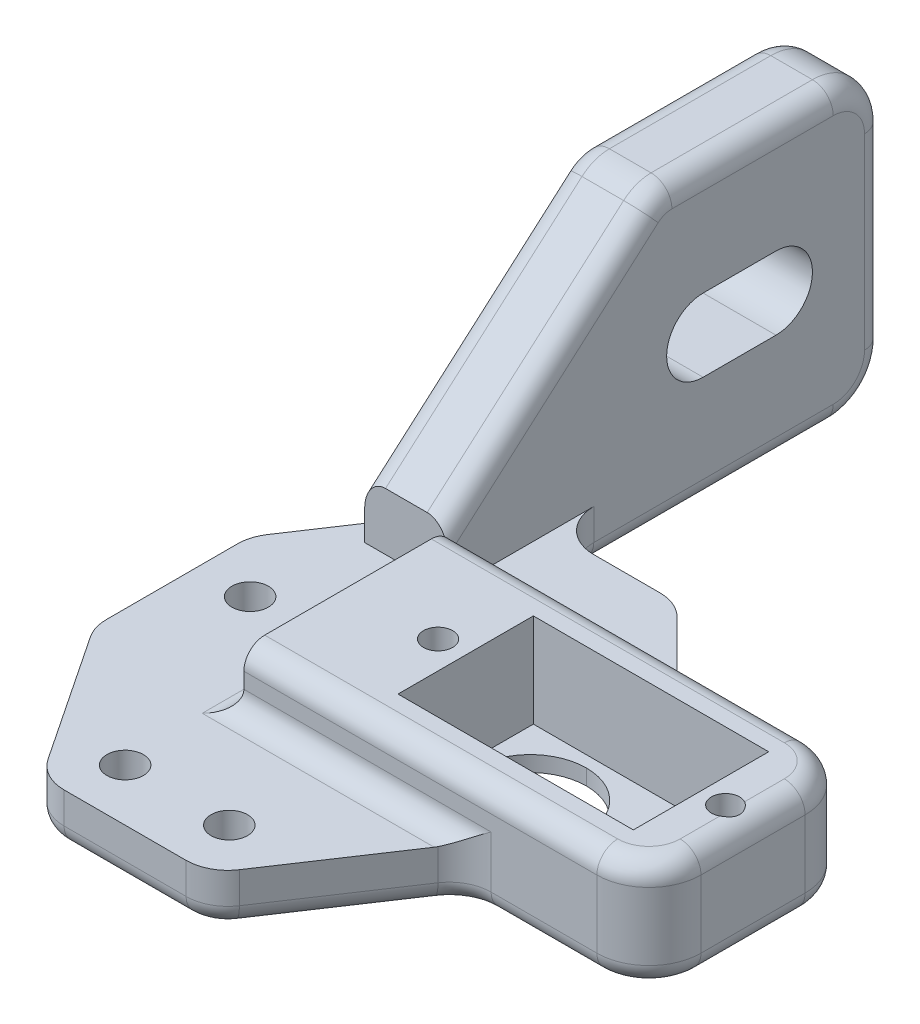
SolidWorks part; units mm, degrees
ref_plane "Front Plane" through (0, 0, 0) normal (0, 0, 1) x (1, 0, 0)
ref_plane "Top Plane" through (0, 0, 0) normal (0, 1, 0) x (1, 0, 0)
ref_plane "Right Plane" through (0, 0, 0) normal (1, 0, 0) x (0, 0, -1)
sketch "Sketch1" plane through (0, 0, 0) normal (0, 1, 0) x (1, 0, 0)
  line L0 (0, 0) -> (20.5534, 0) construction
  line L1 (20.5534, 10) -> (20.5534, -10)
  line L2 (20.5534, 10) -> (-3.4466, 10)
  line L3 (-3.4466, 10) -> (-13.4451, 19.9985)
  line L4 (-13.4451, 19.9985) -> (-29.4451, 19.9985)
  line L5 (-29.4451, 19.9985) -> (-39.4464, 4.9966)
  line L6 (-39.4464, 4.9966) -> (-39.4464, -10.0034)
  line L7 (-39.4464, -10.0034) -> (-29.4451, -25.0053)
  line L8 (-29.4451, -25.0053) -> (-13.4451, -25.0053)
  line L9 (-13.4451, -25.0053) -> (-3.4416, -10)
  line L10 (-3.4416, -10) -> (20.5534, -10)
  point P5 (20.5534, 0)
  dimension "D1" = 20
  dimension "D2" = 24
  dimension "D3" = 14.14
  dimension "D4" = 225
  dimension "D5" = 16
  dimension "D6" = 18.03
  dimension "D7" = 15
  dimension "D8" = 146.31
  dimension "D9" = 18.03
  dimension "D10" = 16
  dimension "D11" = 123.69
  dimension "D12" = 123.69
  dimension "D13" = 18.0341
extrude "Boss-Extrude1" add sketch "Sketch1" against normal blind 5
sketch "Sketch2" plane through (0, 0, 0) normal (0, 1, 0) x (1, 0, 0)
  line L0 (20.5534, 0) -> (-55.4537, 0) construction
  line L1 (20.5534, -10) -> (20.5534, 10) construction
  line L2 (-39.4464, 4.9966) -> (-39.4464, -10.0034) construction
  line L3 (-39.4464, -10.0034) -> (-3.4416, -10) construction
  line L4 (-21.444, -10.0017) -> (-21.444, -20.0053) construction
  line L5 (-26.444, -20.0053) -> (-16.444, -20.0053) construction
  line L6 (-29.4451, -25.0053) -> (-13.4451, -25.0053) construction
  line L8 (-12.9466, 5.4) -> (-2.1466, 5.4)
  line L9 (-12.9466, 5.4) -> (-12.9466, -5.4)
  line L10 (-12.9466, -5.4) -> (-2.1466, -5.4)
  line L11 (-2.1466, 5.4) -> (-2.1466, -5.4)
  line L12 (-12.9466, 5.4) -> (-2.1466, -5.4) construction
  line L13 (-12.9466, -5.4) -> (-2.1466, 5.4) construction
  circle A0 centre (-34.4464, 0) radius 1.75
  circle A1 centre (-26.444, -20.0053) radius 1.75
  circle A2 centre (-16.444, -20.0053) radius 1.75
  point P18 (-21.444, -20.0053)
  point P22 (-7.5466, 0)
  dimension "D2" = 3.5
  dimension "D5" = 3.5
  dimension "D1" = 5
  dimension "D3" = 10
  dimension "D4" = 5
  dimension "D6" = 22.7
  dimension "D7" = 10.8
  dimension "D8" = 10.8
extrude "Cut-Extrude2" cut sketch "Sketch2" along normal through all and the other way through all
fillet "Fillet1" 2 edges at (-12.9466, -2.5, -5.4) (-12.9466, -2.5, 5.4) type full round first side face at (-7.5466, -2.5, -5.4) second side face at (-7.5466, -2.5, 5.4) middle face at (-12.9466, -2.5, 0)
fillet "Fillet2" 2 edges at (-2.1466, -2.5, -5.4) (-2.1466, -2.5, 5.4) type full round first side face at (-4.8466, -2.5, -5.4) second side face at (-4.8466, -2.5, 5.4) middle face at (-2.1466, -2.5, 0)
fillet "Fillet3" 2 edges at (20.5534, -2.5, -10) (20.5534, -2.5, 10) type full round first side face at (8.5534, -2.5, -10) second side face at (8.5559, -2.5, 10) middle face at (20.5534, -2.5, 0)
sketch "Sketch3" plane through (0, 0, 0) normal (0, 1, 0) x (1, 0, 0)
  line L0 (-12.9466, 0) -> (-2.1466, 0) construction
  line L1 (10.5534, 10) -> (-3.4466, 10) construction
  line L2 (-19.0466, -6.5) -> (3.9534, -6.5)
  line L3 (-19.0466, -6.5) -> (-19.0466, 6.5)
  line L4 (-19.0466, 6.5) -> (3.9534, 6.5)
  line L5 (3.9534, -6.5) -> (3.9534, 6.5)
  line L6 (-19.0466, -6.5) -> (3.9534, 6.5) construction
  line L7 (-19.0466, 6.5) -> (3.9534, -6.5) construction
  line L8 (-25.0466, -10) -> (9.9534, -10)
  line L9 (-25.0466, -10) -> (-25.0466, 10)
  line L10 (-25.0466, 10) -> (9.9534, 10)
  line L11 (9.9534, -10) -> (9.9534, 10)
  line L12 (-25.0466, -10) -> (9.9534, 10) construction
  line L13 (-25.0466, 10) -> (9.9534, -10) construction
  arc A0 (-7.5466, 5.4) -> (-7.5466, -5.4) centre (-7.5466, 0) ccw construction
  arc A1 (-7.5466, -5.4) -> (-7.5466, 5.4) centre (-7.5466, 0) ccw construction
  point P8 (-7.5466, 0)
  point P13 (-7.5466, 0)
  dimension "D1" = 6
  dimension "D2" = 13
  dimension "D3" = 23
extrude "Boss-Extrude4" add sketch "Sketch3" along normal blind 5.5
sketch "Sketch4" plane through (0, 0, 0) normal (0, 1, 0) x (1, 0, 0)
  line L4 (-19.0466, 6.5) -> (-19.0466, -6.5)
  line L5 (-19.0466, -6.5) -> (3.9534, -6.5)
  line L6 (3.9534, -6.5) -> (3.9534, 6.5)
  line L7 (3.9534, 6.5) -> (-19.0466, 6.5)
  line L8 (-19.0466, 6.5) -> (-19.0466, -6.5)
  line L9 (-19.0466, -6.5) -> (3.9534, -6.5)
  line L10 (3.9534, -6.5) -> (3.9534, 6.5)
  line L11 (3.9534, 6.5) -> (-19.0466, 6.5)
  dimension "D1" = 0
extrude "Cut-Extrude3" cut sketch "Sketch4" against normal blind 3.5
sketch "Sketch5" plane through (0, 0, 0) normal (0, 1, 0) x (1, 0, 0)
  line L3 (9.9534, 10) -> (9.9534, -10)
  line L4 (9.9534, -10) -> (10.5534, -10)
  line L5 (10.5534, 10) -> (9.9534, 10)
  line L6 (9.9534, 10) -> (9.9534, -10)
  line L7 (9.9534, -10) -> (10.5534, -10)
  line L8 (10.5534, 10) -> (9.9534, 10)
  arc A1 (10.5534, -10) -> (10.5534, 10) centre (10.5534, 0) ccw
  arc A2 (10.5534, -10) -> (10.5534, 10) centre (10.5534, 0) ccw
  dimension "D1" = 0
extrude "Cut-Extrude4" cut sketch "Sketch5" against normal through all body kept at (9.9534, 5.5, 10)
fillet "Fillet4" radius 4 2 edges at (9.9534, 0.25, 10) (9.9534, 0.25, -10)
sketch "Sketch6" plane through (0, 0, -19.9985) normal (0, 0, -1) x (-1, 0, 0)
  line L0 (13.4451, -5) -> (29.4451, -5) construction
  line L1 (25.4451, -5) -> (33.4451, -5)
  line L2 (25.4451, -5) -> (25.4451, 23)
  line L3 (25.4451, 23) -> (33.4451, 23)
  line L4 (33.4451, -5) -> (33.4451, 23)
  line L5 (29.4451, -5) -> (29.4451, 0) construction
  point P8 (29.4451, -2.5)
  dimension "D1" = 4
  dimension "D2" = 4
  dimension "D3" = 28
extrude "Boss-Extrude5" add sketch "Sketch6" along normal blind 32
sketch "Sketch7" plane through (-25.4451, 0, 0) normal (1, 0, 0) x (0, 0, -1)
  line L0 (51.9985, -5) -> (19.9985, -5) construction
  line L1 (51.9985, 23) -> (51.9985, -5) construction
  line L2 (33.4985, 9) -> (42.4985, 9) construction
  circle A0 centre (37.9985, 9) radius 2.5
  circle A1 centre (33.4985, 9) radius 1.3
  circle A2 centre (42.4985, 9) radius 1.3
  point P9 (37.9985, 9)
  dimension "D1" = 5
  dimension "D5" = 2.6
  dimension "D2" = 14
  dimension "D3" = 14
  dimension "D4" = 9
extrude "Cut-Extrude5" cut sketch "Sketch7" against normal through all
fillet "Fillet5" radius 5 2 edges at (-29.4451, -5, -51.9985) (-29.4451, 23, -51.9985)
sketch "Sketch8" plane through (-25.4451, 0, 0) normal (1, 0, 0) x (0, 0, -1)
  line L0 (10, 5.5) -> (19.9985, 23)
  line L1 (19.9985, 23) -> (19.9985, -5)
  line L2 (19.9985, -5) -> (10, -5)
  line L3 (10, -5) -> (10, 5.5)
extrude "Boss-Extrude6" add sketch "Sketch8" against normal up to surface (8 mm away) up to face at (-33.4451, 9, -43.7985)
sketch "Sketch9" plane through (-25.4451, 0, 0) normal (1, 0, 0) x (0, 0, -1)
  line L0 (40.4985, 9) -> (35.4985, 9) construction
  line L2 (44.9985, 12.5) -> (30.9985, 12.5)
  line L3 (44.9985, 12.5) -> (44.9985, 5.5)
  line L4 (44.9985, 5.5) -> (30.9985, 5.5)
  line L5 (30.9985, 12.5) -> (30.9985, 5.5)
  line L6 (44.9985, 12.5) -> (30.9985, 5.5) construction
  line L7 (44.9985, 5.5) -> (30.9985, 12.5) construction
  circle A0 centre (37.9985, 9) radius 2.5 construction
  point P5 (37.9985, 9)
  dimension "D1" = 7
  dimension "D2" = 14
extrude "Cut-Extrude6" cut sketch "Sketch9" against normal blind 7
fillet "Fillet7" 2 edges at (-28.9451, 5.5, -44.9985) (-28.9451, 12.5, -44.9985) type full round first side face at (-28.9451, 5.5, -37.9985) second side face at (-28.9451, 12.5, -37.9985) middle face at (-28.9451, 9, -44.9985)
fillet "Fillet8" 2 edges at (-28.9451, 12.5, -30.9985) (-28.9451, 5.5, -30.9985) type full round first side face at (-28.9451, 12.5, -36.2485) second side face at (-28.9451, 5.5, -36.2485) middle face at (-28.9451, 9, -30.9985)
sketch "Sketch10" plane through (-25.4451, 0, 0) normal (1, 0, 0) x (0, 0, -1)
  line L0 (10, 5.5) -> (29.9985, 23)
  line L1 (46.9985, 23) -> (19.9985, 23) construction
  line L2 (29.9985, 23) -> (19.9985, 23)
  line L3 (19.9985, 23) -> (10, 5.5)
  dimension "D1" = 10
extrude "Cut-Extrude7" cut sketch "Sketch10" against normal through all
fillet "Fillet9" radius 4 6 edges at (-13.4451, -2.5, 25.0053) (-29.4451, -2.5, 25.0053) (-39.4464, -2.5, 10.0034) (-39.4464, -2.5, -4.9966) (-33.4451, -2.5, -13.9985) (-29.4451, 23, -29.9985)
fillet "Fillet10" radius 4 1 edges at (-3.4416, -2.5, 10)
fillet "Fillet11" radius 4 3 edges at (-25.4451, -2.5, -19.9985) (-13.4451, -2.5, -19.9985) (-3.4466, -2.5, -10)
sketch "Sketch11" plane through (0, -3.5, 0) normal (0, 1, 0) x (1, 0, 0)
  line L0 (-19.0466, -6.5) -> (3.9534, -6.5) construction
  line L1 (-19.0466, 6.5) -> (-13.7466, 6.5)
  line L2 (-19.0466, 6.5) -> (-19.0466, -6.5)
  line L3 (-19.0466, -6.5) -> (-13.7466, -6.5)
  line L4 (-13.7466, 6.5) -> (-13.7466, -6.5)
  line L5 (-19.0466, 0) -> (-13.7466, 0) construction
  circle A0 centre (-16.3966, 0) radius 1.4
  dimension "D2" = 2.8
  dimension "D1" = 5.3
extrude "Boss-Extrude7" add sketch "Sketch11" along normal up to surface (9 mm away) up to face at (-2.7705, 5.5, 0)
sketch "Sketch12" plane through (0, 5.5, 0) normal (0, 1, 0) x (1, 0, 0)
  line L0 (5.9534, 10) -> (13.8534, 10)
  line L1 (5.9534, -10) -> (13.8534, -10)
  line L2 (13.8534, -10) -> (13.8534, 10)
  line L3 (9.9534, -6) -> (9.9534, 6) construction
  line L4 (9.9534, -6) -> (9.9534, 6)
  arc A0 (5.9534, -10) -> (9.9534, -6) centre (5.9534, -6) ccw construction
  arc A1 (9.9534, 6) -> (5.9534, 10) centre (5.9534, 6) ccw construction
  arc A2 (5.9534, -10) -> (9.9534, -6) centre (5.9534, -6) ccw
  arc A3 (9.9534, 6) -> (5.9534, 10) centre (5.9534, 6) ccw
  dimension "D1" = 7.9
extrude "Boss-Extrude8" add sketch "Sketch12" against normal up to surface (10.5 mm away) up to face at (-17.626, -5, -4.0268)
sketch "Sketch13" plane through (0, 5.5, 0) normal (0, 1, 0) x (1, 0, 0)
  line L0 (-16.3966, 0) -> (11.2034, 0) construction
  circle A0 centre (11.2034, 0) radius 1.35
  dimension "D2" = 2.7
  dimension "D1" = 27.6
extrude "Cut-Extrude12" cut sketch "Sketch13" against normal up to surface (9 mm away) up to face at (-16.3966, -3.5, 1.4)
fillet "Fillet12" radius 5 2 edges at (13.8534, 0.25, 10) (13.8534, 0.25, -10)
sketch "Sketch14" plane through (0, 5.5, 0) normal (0, 1, 0) x (1, 0, 0)
  line L0 (-13.7466, -6.5) -> (3.9534, -6.5) construction
  line L1 (3.9534, 6.5) -> (8.8534, 6.5)
  line L2 (3.9534, 6.5) -> (3.9534, -6.5)
  line L3 (3.9534, -6.5) -> (8.8534, -6.5)
  line L4 (8.8534, 6.5) -> (8.8534, -6.5)
  dimension "D1" = 4.9
extrude "Cut-Extrude13" cut sketch "Sketch14" against normal up to surface (9 mm away) up to face at (-7.5466, -3.5, 0)
fillet "Fillet14" radius 2 40 edges at (-33.4451, 13.7551, -19.4337) (-33.4451, 22.7444, -30.0945) (-33.4451, 23, -39.25) (-33.4451, 21.5355, -50.534) (-33.4451, 9, -51.9985) (-33.4451, -3.5355, -50.534) (-25.4451, 13.7551, -19.4337) (-25.4451, 22.7444, -30.0945) (-25.4451, 23, -39.25) (-25.4451, 21.5355, -50.534) (-25.4451, 9, -51.9985) (-25.4451, -3.5355, -50.534) (-8.0966, 5.5, 10) (12.3889, 5.5, 8.5355) (13.8534, 5.5, 0) (12.3889, 5.5, -8.5355) (12.3889, -5, -8.5355) (3.5318, -5, -10) (-3.3205, -5, -10.3045) (-8.4459, -5, -14.9992) (-13.5713, -5, -19.694) (-18.2736, -5, -19.9985) (-24.2736, -5, -21.1701) (-25.4451, -5, -35.4985) (-33.4451, -5, -31.104) (-33.6168, -5, -14.0504) (-36.4457, -5, -9.4975) (-39.2747, -5, -4.9446) (-39.4464, -5, 2.5034) (-39.2747, -5, 9.9514) (-34.7036, -5, 17.1176) (-29.1918, -5, 24.532) (-21.4451, -5, 25.0053) (-13.6984, -5, 24.532) (-8.4434, -5, 17.5026) (-3.1883, -5, 10.4733) (3.7762, -5, 10) (12.3889, -5, 8.5355) (13.8534, -5, 0) (-8.0966, 5.5, -10)
fillet "Fillet15" radius 2 2 edges at (-25.0466, 0, 0) (-13.4182, 0, -10)
fillet "Fillet16" radius 2 1 edges at (-14.1738, 0, 10)
